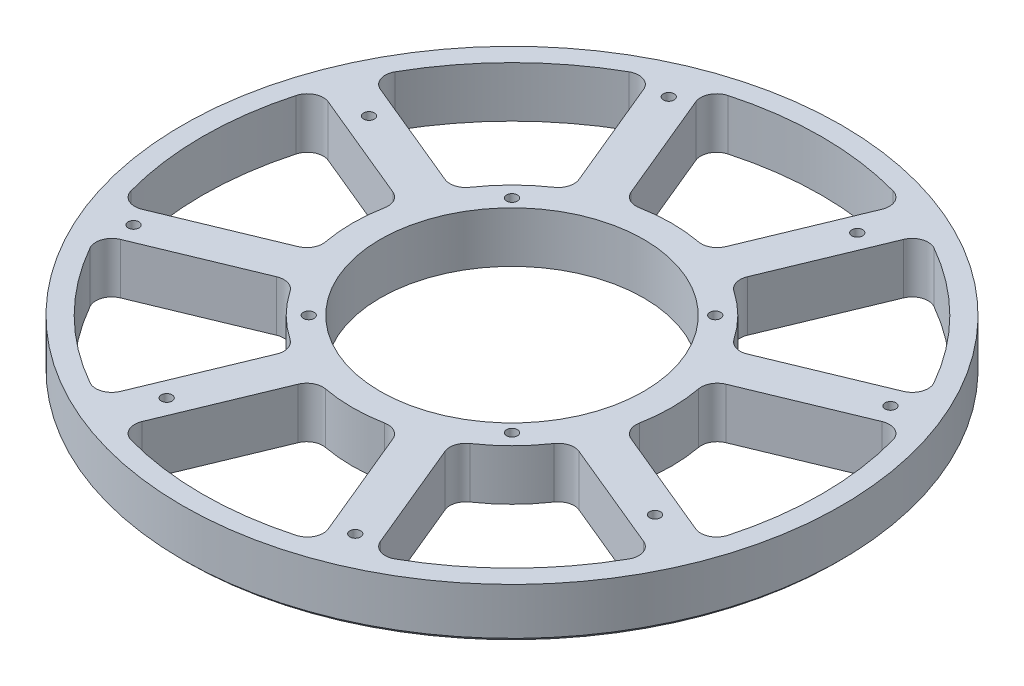
SolidWorks part; units mm, degrees
material "6061-T6 (SS)"
ref_plane "Front Plane" through (0, 0, 0) normal (0, 0, 1) x (1, 0, 0)
ref_plane "Top Plane" through (0, 0, 0) normal (0, 1, 0) x (1, 0, 0)
ref_plane "Right Plane" through (0, 0, 0) normal (1, 0, 0) x (0, 0, -1)
sketch "Sketch2" plane through (0, 0, 0) normal (1, 0, 0) x (0, 0, -1)
  line L0 (0, 0) -> (-82.55, 0)
  line L1 (-82.55, 0) -> (-82.55, 12.7)
  line L2 (-82.55, 12.7) -> (0, 12.7)
  line L5 (0, 12.7) -> (0, 0)
  dimension "D1" = 82.55
  dimension "D2" = 12.7
ref_axis "Axis1" through (0, -0.635, 0) along (0, 1, 0)
revolve "Revolve1" add sketch "Sketch2" angle 360 about axis through (0, -0.635, 0) along (0, 1, 0)
hole_wizard "#6-32 Tapped Hole1" positions "Sketch6" profile "Sketch7" tap size "#6-32" standard "ANSI Inch" end condition through all
sketch "Sketch6" plane through (0, 12.7, 0) normal (0, 1, 0) x (1, 0, 0)
  line L0 (0, 0) -> (-53.438, 129.0108) construction
  line L2 (0, 0) -> (0, 109.0908) construction
  line L3 (0, 0) -> (-76.2663, 31.5905) construction
  line L4 (0, 0) -> (-68.4315, 68.4315) construction
  circle A0 centre (0, 0) radius 82.55 construction
  point P0 (-27.7637, 67.0275)
  point P18 (-61.1608, 25.3336)
  point P27 (-25.4558, 25.4558)
  dimension "D1" = 22.5
  dimension "D2" = 72.55
  dimension "D3" = 45
  dimension "D4" = 66.2
  dimension "D6" = 22.5
  dimension "D5" = 36
sketch "Sketch7" plane through (-27.7637, 12.7, -67.0275) normal (1, 0, 0) x (0, 0, 1)
  line L0 (0, 0) -> (0, 12.7)
  line L1 (0, 12.7) -> (1.3525, 12.7)
  line L2 (1.3525, 12.7) -> (1.3525, 0)
  line L5 (1.3525, 0) -> (0, 0)
  line L11 (0, -6.35) -> (0, 107.95) construction
  dimension "Thread Major Dia." = 2.7051
  dimension "Thru Tap Drill Depth" = 12.7
pattern_circular "CirPattern3" count 4 over 360 about axis through (0, -0.635, 0) along (0, 1, 0) of "#6-32 Tapped Hole1"
sketch "Sketch8" plane through (0, 12.7, 0) normal (0, 1, 0) x (1, 0, 0)
  line L4 (0, 0) -> (0, 93.9995) construction
  line L5 (0, 0) -> (113.8372, 0) construction
  line L6 (-10.5679, 38.5787) -> (-24.996, 73.4112)
  line L7 (10.5679, 38.5787) -> (24.996, 73.4112)
  line L8 (0, 0) -> (-27.7637, 67.0275) construction
  arc A0 (-10.5679, 38.5787) -> (10.5679, 38.5787) centre (0, 0) cw
  arc A1 (-24.996, 73.4112) -> (24.996, 73.4112) centre (0, 0) cw
  circle A2 centre (0, 0) radius 82.55 construction
  dimension "D1" = 40
  dimension "D2" = 5
  dimension "D3" = 5
extrude "Cut-Extrude1" cut sketch "Sketch8" against normal through all
fillet "Fillet1" radius 4 4 edges at (10.5679, 6.35, -38.5787) (24.996, 6.35, -73.4112) (-10.5679, 6.35, -38.5787) (-24.996, 6.35, -73.4112)
pattern_circular "CirPattern4" count 8 over 360 about axis through (0, -0.635, 0) along (0, 1, 0) of "Cut-Extrude1", "Fillet1"
chamfer "Chamfer2" distance 1 angle 45 1 edges at (0, 0, -82.55)
sketch "Sketch9" plane through (0, 12.7, 0) normal (0, 1, 0) x (1, 0, 0)
  circle A0 centre (0, 0) radius 33
  dimension "D1" = 66
extrude "Cut-Extrude2" cut sketch "Sketch9" against normal through all
equation "\"TubeDiameter\" = 6.500in"
equation "\"D1@Sketch2\"=\"TubeDiameter\"/2"
equation "\"D2@Sketch6\"=\"TubeDiameter\"/2-10mm"
